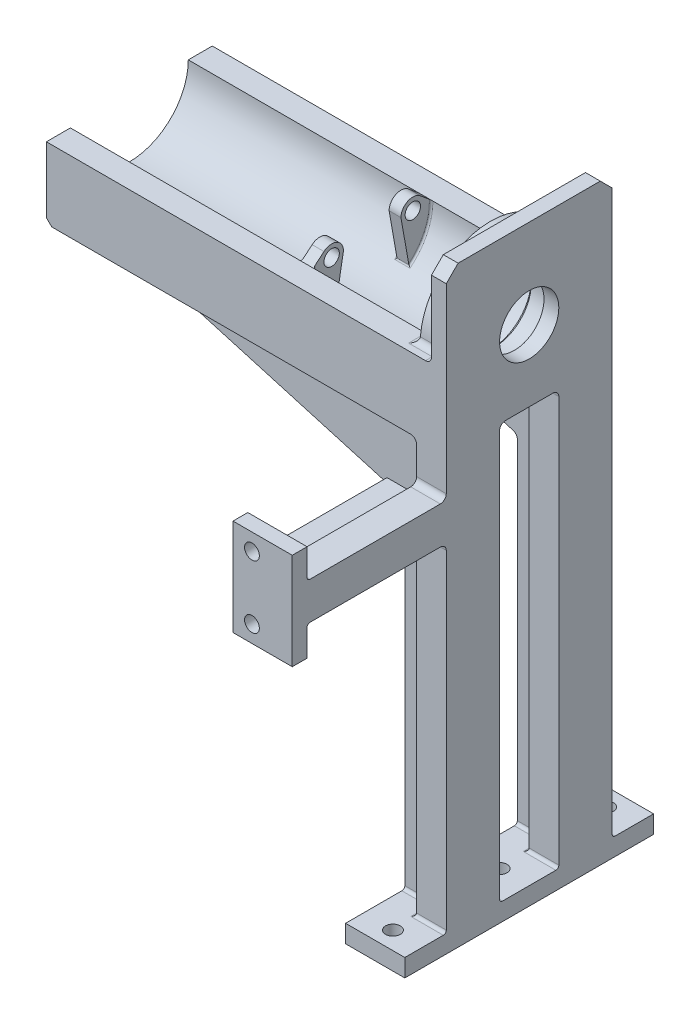
SolidWorks part; units mm, degrees
material "PLA"
ref_plane "Front Plane" through (0, 0, 0) normal (0, 0, 1) x (1, 0, 0)
ref_plane "Top Plane" through (0, 0, 0) normal (0, 1, 0) x (1, 0, 0)
ref_plane "Right Plane" through (0, 0, 0) normal (1, 0, 0) x (0, 0, -1)
sketch "Profile-Sketch" plane through (0, 0, 0) normal (1, 0, 0) x (0, 0, -1)
  line L0 (0, 0) -> (50000, 0) construction
  line L1 (0, 0) -> (0, 50000) construction
  line L2 (0, 0) -> (0, 114.3) construction
  line L3 (0, 114.3) -> (63.5, 165.1) construction
  line L4 (63.5, 165.1) -> (190.5, 165.1) construction
  circle A0 centre (50.8, 107.95) radius 8.763 construction
  circle A2 centre (50.8, 107.95) radius 3.175 construction
  circle A3 centre (50.8, 107.95) radius 12.4968 construction
  dimension "D1" = 17.526
  dimension "D8" = 6.35
  dimension "D9" = 24.9936
  dimension "D2" = 107.95
  dimension "D3" = 114.3
  dimension "D4" = 50.8
  dimension "D5" = 63.5
  dimension "D6" = 50.8
  dimension "D7" = 127
sketch "Sketch3" plane through (0, 0, 0) normal (1, 0, 0) x (0, 0, -1)
  line L10 (33.02, 127) -> (33.02, 92.71)
  line L11 (33.02, 92.71) -> (68.58, 92.71)
  line L12 (68.58, 92.71) -> (68.58, 127)
  line L13 (68.58, 127) -> (33.02, 127)
  circle A1 centre (50.8, 107.95) radius 6.35
  dimension "D9" = 12.7
  dimension "D1" = 17.78
  dimension "D2" = 17.78
  dimension "D3" = 19.05
  dimension "D4" = 15.24
extrude "Base-Plate" add sketch "Sketch3" against normal blind 3.175
sketch "Sketch5" plane through (-3.175, 0, 0) normal (-1, 0, 0) x (0, 0, 1)
  circle A0 centre (-50.8, 107.95) radius 7.9502
  circle A1 centre (-50.8, 107.95) radius 15.113
  dimension "D1" = 15.9004
  dimension "D2" = 30.226
extrude "Bearing-Feature" add sketch "Sketch5" along normal blind 5.08
sketch "Motor-Mount" plane through (-3.175, 0, 0) normal (-1, 0, 0) x (0, 0, 1)
  line L0 (-63.4365, 107.95) -> (-38.1635, 107.95) construction
  line L1 (-63.4365, 107.95) -> (-68.58, 107.95)
  line L2 (-68.58, 92.71) -> (-68.58, 127) construction
  line L3 (-68.58, 107.95) -> (-68.58, 92.71)
  line L4 (-68.58, 92.71) -> (-33.02, 92.71)
  line L5 (-33.02, 92.71) -> (-33.02, 107.95)
  line L6 (-33.02, 127) -> (-33.02, 92.71) construction
  line L7 (-33.02, 107.95) -> (-38.1635, 107.95)
  arc A0 (-63.4365, 107.95) -> (-38.1635, 107.95) centre (-50.8, 107.95) ccw
  dimension "D1" = 25.273
extrude "Motor-Mount-Feature" add sketch "Motor-Mount" along normal blind 82.55
ref_plane "Motor-Mount-Plane" through (-36.195, 0, 0) normal (-1, 0, 0) x (0, 0, 1)
sketch "Sketch6" plane through (-36.195, 0, 0) normal (-1, 0, 0) x (0, 0, 1)
  line L0 (-50.8, 101.6) -> (-50.8, 50101.6) construction
  line L1 (-50.8, 107.95) -> (-63.4365, 107.95) construction
  line L2 (-63.4365, 107.95) -> (-61.1382, 109.8907)
  line L3 (-56.9595, 107.95) -> (-58.6987, 98.0864)
  line L4 (-58.6987, 98.0864) -> (-63.4365, 98.0864)
  line L5 (-63.4365, 98.0864) -> (-63.4365, 107.95)
  line L6 (-38.1635, 98.0864) -> (-38.1635, 107.95)
  line L7 (-42.9013, 98.0864) -> (-38.1635, 98.0864)
  line L8 (-44.6405, 107.95) -> (-42.9013, 98.0864)
  line L9 (-38.1635, 107.95) -> (-40.4618, 109.8907)
  circle A0 centre (-59.4995, 107.95) radius 1.651
  arc A1 (-56.9595, 107.95) -> (-61.1382, 109.8907) centre (-59.4995, 107.95) ccw
  arc A2 (-63.4365, 107.95) -> (-38.1635, 107.95) centre (-50.8, 107.95) ccw construction
  arc A3 (-44.6405, 107.95) -> (-40.4618, 109.8907) centre (-42.1005, 107.95) cw
  circle A4 centre (-42.1005, 107.95) radius 1.651
  dimension "D2" = 3.302
  dimension "D3" = 5.08
  dimension "D1" = 17.399
  dimension "D4" = 100
extrude "Motor-Mount-Holes" add sketch "Sketch6" against normal blind 2.54
sketch "Sketch7" plane through (0, 0, 0) normal (1, 0, 0) x (0, 0, -1)
  line L0 (68.58, 92.71) -> (68.58, 0)
  line L1 (-200000, 0) -> (250000, 0) construction
  line L2 (68.58, 92.71) -> (57.15, 92.71)
  line L3 (33.02, 92.71) -> (68.58, 92.71) construction
  line L4 (57.15, 92.71) -> (57.15, 3.175)
  line L7 (50.8, -1101.6) -> (50.8, 0) construction
  line L11 (57.15, 3.175) -> (44.45, 3.175)
  line L13 (33.02, 0) -> (68.58, 0)
  line L14 (50.8, 3.175) -> (50.8, 50101.6) construction
  line L15 (44.45, 92.71) -> (44.45, 3.175)
  line L16 (33.02, 92.71) -> (44.45, 92.71)
  line L17 (33.02, 92.71) -> (33.02, 0)
  dimension "D1" = 11.43
  dimension "D2" = 3.175
extrude "Mount-Legs" add sketch "Sketch7" against normal blind 6.35
sketch "Sketch8" plane through (0, 0, 0) normal (0, -1, 0) x (1, 0, 0)
  line L0 (0, -24.13) -> (0, -77.47)
  line L1 (0, 0) -> (0, -63.5) construction
  line L2 (0, -24.13) -> (-12.7, -24.13)
  line L3 (-12.7, -24.13) -> (-12.7, -77.47)
  line L4 (-12.7, -77.47) -> (0, -77.47)
  line L5 (0, -63.5) -> (0, -190.5) construction
  line L6 (-6.35, -33.02) -> (0, -33.02) construction
  line L7 (-6.35, -68.58) -> (0, -68.58) construction
  dimension "D1" = 12.7
  dimension "D2" = 8.89
  dimension "D3" = 8.89
extrude "Mounting-LegFeet" add sketch "Sketch8" against normal blind 3.81
ref_plane "Single-Leg-MidPlane" through (0, 0, -62.865) normal (0, 0, -1) x (-1, 0, 0)
ref_plane "Mount-MidPlane" through (0, 0, -50.8) normal (0, 0, -1) x (-1, 0, 0)
sketch "Sketch9" plane through (0, 0, -62.865) normal (0, 0, -1) x (-1, 0, 0)
  line L0 (69.85, 92.71) -> (12.7, 76.2)
  line L1 (0, 3.81) -> (0, 127) construction
  line L2 (12.7, 76.2) -> (12.7, 8.89)
  line L4 (85.725, 92.71) -> (6.35, 92.71) construction
  line L5 (69.85, 92.71) -> (6.35, 92.71)
  line L6 (6.35, 92.71) -> (6.35, 3.81)
  line L8 (12.7, 8.89) -> (12.7, 3.81)
  line L9 (12.7, 3.81) -> (6.35, 3.81)
  line L10 (0, 0) -> (0, 114.3) construction
  line L22 (6.35, 3.81) -> (6.35, 92.71) construction
  dimension "D1" = 69.85
  dimension "D2" = 16.51
  dimension "D3" = 12.7
  dimension "D5" = 5.08
extrude "Leg-Stiffener" add sketch "Sketch9" along normal mid plane 3.81
mirror "Mirror1" about plane through (0, 0, -50.8) normal (0, 0, -1) of "Leg-Stiffener"
sketch "Sketch10" plane through (0, 0, 0) normal (0, -1, 0) x (1, 0, 0)
  line L0 (0, 0) -> (0, -63.5) construction
  line L1 (0, -63.2968) -> (0, -38.3032) construction
  line L2 (0, -63.5) -> (0, -190.5) construction
  line L3 (0, -50.8) -> (-12.7, -50.8) construction
  line L4 (0, -24.13) -> (0, -77.47) construction
  line L5 (-12.7, -24.13) -> (-12.7, -77.47) construction
  circle A0 centre (-6.35, -27.94) radius 1.5875
  circle A1 centre (-6.35, -50.8) radius 1.5875
  circle A2 centre (-6.35, -73.66) radius 1.5875
  dimension "D2" = 3.175
  dimension "D4" = 3.175
  dimension "D5" = 3.175
  dimension "D1" = 6.35
  dimension "D3" = 6.35
  dimension "D6" = 6.35
  dimension "D7" = 27.94
  dimension "D8" = 50.8
  dimension "D9" = 73.66
  dimension "D10" = 22.86
  dimension "D11" = 22.86
extrude "Bottom-Mounting-Holes" cut sketch "Sketch10" against normal blind 12.7
sketch "Sketch11" plane through (0, 0, 0) normal (1, 0, 0) x (0, 0, -1)
  line L0 (33.02, 84.201) -> (0, 84.201)
  line L1 (33.02, 127) -> (33.02, 3.81) construction
  line L2 (0, 84.201) -> (0, 76.2)
  line L3 (0, 76.2) -> (33.02, 76.2)
  line L4 (33.02, 76.2) -> (33.02, 84.201)
  line L5 (0, -200000) -> (0, 250000) construction
  line L8 (24.13, 0) -> (77.47, 0) construction
  dimension "D1" = 8.001
  dimension "D2" = 76.2
extrude "Mount-SideArm" add sketch "Sketch11" against normal up to surface (6.35 mm away) up to face at (-6.35, 48.26, -34.925)
sketch "Sketch12" plane through (0, 0, 0) normal (0, 0, 1) x (1, 0, 0)
  line L0 (0, 90.551) -> (-12.7, 90.551)
  line L1 (0, 104.775) -> (0, 111.125) construction
  line L2 (-12.7, 90.551) -> (-12.7, 69.85)
  line L3 (-12.7, 69.85) -> (0, 69.85)
  line L4 (0, 0) -> (0, 114.3) construction
  line L5 (0, 69.85) -> (0, 90.551)
  line L6 (-6.35, 84.201) -> (0, 84.201) construction
  line L7 (-6.35, 76.2) -> (0, 76.2) construction
  dimension "D1" = 6.35
  dimension "D2" = 6.35
  dimension "D3" = 12.7
extrude "SideMount-Plate" add sketch "Sketch12" against normal blind 3.175
ref_plane "Plane4" through (0, 80.2005, 0) normal (0, 1, 0) x (1, 0, 0)
sketch "Sketch13" plane through (0, 80.2005, 0) normal (0, 1, 0) x (1, 0, 0)
  line L2 (-12.7, 33.02) -> (-12.7, 5.08)
  line L3 (-12.7, 5.08) -> (-12.7, 0)
  line L4 (-12.7, 0) -> (-6.35, 0)
  line L5 (-6.35, 33.02) -> (-6.35, 3.175) construction
  line L6 (0, 0) -> (-12.7, 0) construction
  line L7 (-6.35, 0) -> (-6.35, 33.02)
  line L9 (0, -200000) -> (0, 250000) construction
  line L10 (-85.725, 33.02) -> (-3.175, 33.02) construction
  line L11 (-12.7, 33.02) -> (-6.35, 33.02)
  dimension "D2" = 12.7
  dimension "D4" = 5.08
extrude "Arm-Stiffener" add sketch "Sketch13" along normal mid plane 3.81
sketch "Sketch14" plane through (0, 0, 0) normal (0, 0, -1) x (-1, 0, 0)
  line L3 (0, 90.551) -> (0, 69.85) construction
  line L4 (0, 69.85) -> (12.7, 69.85) construction
  line L5 (12.7, 69.85) -> (12.7, 90.551) construction
  line L15 (0, 90.551) -> (0, 69.85) construction
  line L16 (0, 69.85) -> (12.7, 69.85) construction
  line L17 (12.7, 69.85) -> (12.7, 90.551) construction
  line L25 (0, 116.713) -> (0, 99.187) construction
  line L26 (0, 0) -> (0, 114.3) construction
  line L29 (0, 0) -> (12.7, 0) construction
  circle A0 centre (8.636, 86.9315) radius 1.5875
  circle A1 centre (8.636, 73.4695) radius 1.5875
  point P1 (12.7, 80.2005)
  dimension "D1" = 3.175
  dimension "D2" = 3.175
  dimension "D3" = 8.636
  dimension "D4" = 8.636
  dimension "D5" = 73.4695
  dimension "D6" = 86.9315
  dimension "D7" = 6.731
  dimension "D8" = 6.731
extrude "Side-Mount-Holes" cut sketch "Sketch14" along normal up to surface (3.175 mm away) up to face at (-6.35, 74.7818, -3.175)
fillet "Fillet2" radius 0.635 19 edges at (-6.35, 3.81, -59.055) (-6.35, 3.81, -34.925) (-3.175, 3.81, -33.02) (-3.175, 3.81, -44.45) (-3.175, 3.81, -68.58) (-3.175, 3.81, -57.15) (-6.35, 3.81, -66.675) (-9.525, 3.81, -60.96) (-9.525, 3.81, -64.77) (-6.35, 3.81, -42.545) (-9.525, 3.81, -36.83) (-9.525, 3.81, -40.64) (-3.175, 84.201, -3.175) (-3.175, 76.2, -3.175) (-6.35, 83.1532, -3.175) (-6.35, 77.2478, -3.175) (-9.525, 78.2955, -3.175) (-9.525, 82.1055, -3.175) (-12.7, 78.2955, -18.0975)
fillet "Fillet3" radius 1.27 23 edges at (-6.536, 78.1095, -3.361) (-6.536, 82.2915, -3.361) (-6.35, 82.1055, -18.415) (-6.35, 78.2955, -18.415) (-38.1, 92.71, -64.77) (-6.35, 92.71, -66.675) (-6.35, 92.71, -34.925) (-6.35, 92.71, -42.545) (-6.35, 92.71, -59.055) (-38.1, 92.71, -60.96) (-38.1, 92.71, -36.83) (-38.1, 92.71, -40.64) (-6.35, 48.5775, -64.77) (-6.35, 48.5775, -60.96) (-6.35, 48.5775, -36.83) (-6.35, 48.5775, -40.64) (-6.35, 80.2005, -33.02) (-6.536, 3.996, -40.826) (-6.536, 3.996, -36.644) (-6.536, 3.996, -60.774) (-6.536, 3.996, -64.956) (-69.85, 92.71, -38.735) (-69.85, 92.71, -62.865)
fillet "Fillet4" radius 1.27 4 edges at (-3.81, 92.71, -44.45) (-3.81, 92.71, -57.15) (-3.175, 76.2, -33.02) (-3.175, 84.201, -33.02)
fillet "Fillet5" radius 1.27 10 edges at (-8.255, 95.3135, -50.8) (-3.175, 107.95, -67.2465) (-3.175, 123.063, -50.8) (-3.175, 107.95, -34.3535) (-5.715, 107.95, -35.687) (-8.255, 107.95, -36.9252) (-5.715, 107.95, -65.913) (-8.255, 107.95, -64.6748) (-12.7, 76.2, -62.865) (-12.7, 76.2, -38.735)
fillet "Fillet6" radius 0.381 7 edges at (-3.175, 107.95, -42.8498) (-34.925, 98.0864, -42.9013) (-34.925, 98.0864, -58.6987) (-33.655, 102.4788, -62.1906) (-33.655, 102.4788, -39.4094) (-36.195, 102.4788, -39.4094) (-36.195, 102.4788, -62.1906)
chamfer "Chamfer1" distance 0.762 angle 45 1 edges at (-8.255, 107.95, -42.8498)
chamfer "Chamfer2" distance 2.54 angle 45 2 edges at (-1.5875, 127, -33.02) (-1.5875, 127, -68.58)
chamfer "Chamfer4" distance 1.143 angle 45 1 edges at (-85.725, 92.71, -50.8)
equation "\"D2@Sketch14\"=\"D1@Sketch14\""
